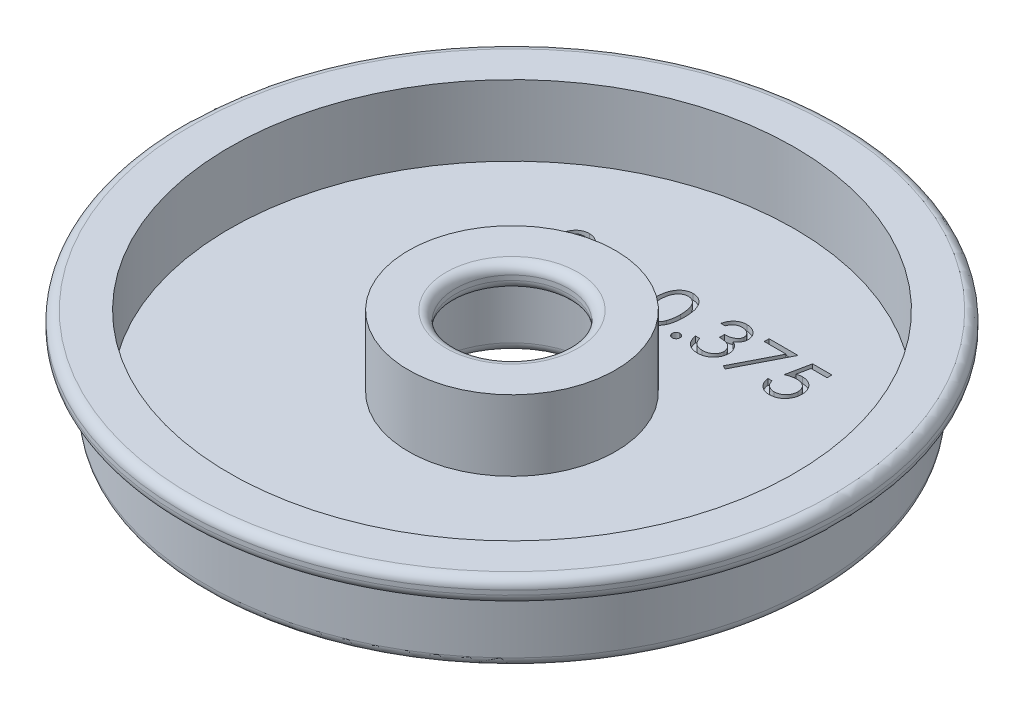
SolidWorks part; units mm, degrees
ref_plane "Front Plane" through (0, 0, 0) normal (0, 0, 1) x (1, 0, 0)
ref_plane "Top Plane" through (0, 0, 0) normal (0, 1, 0) x (1, 0, 0)
ref_plane "Right Plane" through (0, 0, 0) normal (1, 0, 0) x (0, 0, -1)
sketch "Sketch1" plane through (0, 0, 0) normal (0, 0, 1) x (1, 0, 0)
  line L0 (0, 0) -> (0, 11.1543)
  line L3 (13.97, 15.9118) -> (13.97, 6.3868)
  line L4 (13.97, 6.3868) -> (38.1, 6.3868)
  line L5 (38.1, 6.3868) -> (38.1, 15.9118)
  line L8 (40.005, 3.2118) -> (12.065, 3.2118)
  line L9 (41.275, 4.4818) -> (41.275, 11.5037)
  line L10 (42.545, 12.7737) -> (43.18, 12.7737)
  line L11 (44.45, 14.0437) -> (44.45, 14.6418)
  line L12 (38.1, 15.9118) -> (43.18, 15.9118)
  line L13 (13.97, 15.9118) -> (8.89, 15.9118)
  line L14 (7.62, 14.6418) -> (7.62, 14.0068)
  line L15 (10.795, 4.4818) -> (10.795, 11.4668)
  line L16 (9.525, 12.7368) -> (8.89, 12.7368)
  arc A0 (43.18, 15.9118) -> (44.45, 14.6418) centre (43.18, 14.6418) cw
  arc A1 (44.45, 14.0437) -> (43.18, 12.7737) centre (43.18, 14.0437) cw
  arc A2 (42.545, 12.7737) -> (41.275, 11.5037) centre (42.545, 11.5037) ccw
  arc A3 (41.275, 4.4818) -> (40.005, 3.2118) centre (40.005, 4.4818) cw
  arc A4 (12.065, 3.2118) -> (10.795, 4.4818) centre (12.065, 4.4818) cw
  arc A5 (10.795, 11.4668) -> (9.525, 12.7368) centre (9.525, 11.4668) ccw
  arc A6 (8.89, 12.7368) -> (7.62, 14.0068) centre (8.89, 14.0068) cw
  arc A7 (7.62, 14.6418) -> (8.89, 15.9118) centre (8.89, 14.6418) cw
  dimension "D10" = 1.27
  dimension "D1" = 3.175
  dimension "D2" = 6.35
  dimension "D3" = 3.175
  dimension "D4" = 6.35
  dimension "D5" = 3.175
  dimension "D6" = 13.97
  dimension "D7" = 38.1
  dimension "D8" = 3.1382
  dimension "D9" = 3.175
  dimension "D11" = 9.525
  dimension "D12" = 9.525
revolve "Revolve2" add sketch "Sketch1" angle 360 about L0 region at (13.5804, 11.1493, 0)
sketch "Sketch2" plane through (0, 6.3868, 0) normal (0, 1, 0) x (1, 0, 0)
  text T0 "3 x 0.375" font "Century Gothic" height in points 24
  point P1 (-15.6461, 17.1863)
  point P2 (0, 0)
  point P3 (0, 0)
  point P4 (0, 0)
  point P5 (0, 0)
extrude "Cut-Extrude1" cut sketch "Sketch2" against normal blind 0.7937
